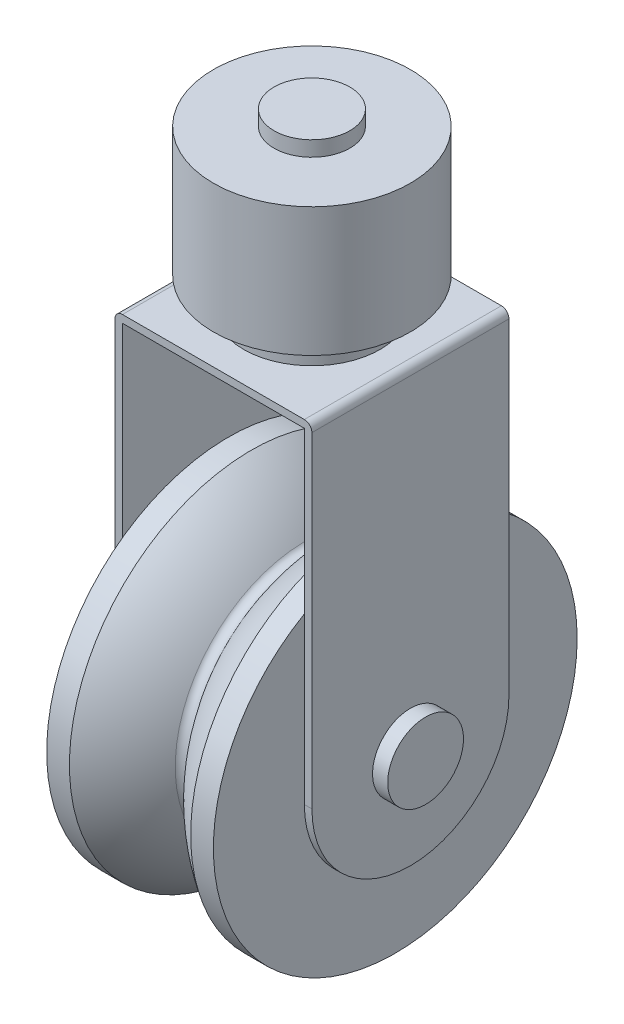
SolidWorks part; units mm, degrees
ref_plane "前视基准面" through (0, 0, 0) normal (0, 0, 1) x (1, 0, 0)
ref_plane "上视基准面" through (0, 0, 0) normal (0, 1, 0) x (1, 0, 0)
ref_plane "右视基准面" through (0, 0, 0) normal (1, 0, 0) x (0, 0, -1)
other "Configuration Table"
sketch "草图1" plane through (0, 0, 0) normal (0, 0, 1) x (1, 0, 0)
  line L0 (0, 0) -> (0, 16)
  line L1 (8, 24) -> (11, 24)
  line L2 (11, 24) -> (11, 0)
  line L3 (11, 0) -> (-11, 0)
  line L4 (11, 24) -> (8, 24)
  line L5 (-11, 24) -> (-11, 0)
  line L6 (-8, 24) -> (-11, 24)
  spline S0 degree 2 poles (0, 16) (3.2003, 21.0713) (8, 24) knots 0 0 0 0.822363 0.822363 0.822363
  spline S1 degree 2 poles (0, 16) (-3.2003, 21.0713) (-8, 24) knots 0 0 0 0.822363 0.822363 0.822363
  dimension "D1" = 24
  dimension "D2" = 11
revolve "旋转1" add sketch "草图1" angle 360 about L3 region at (-5.8476, 10.9127, 0) region at (5.8476, 10.9127, 0)
fillet "圆角1" radius 1 1 edges at (0, 0, -16)
sketch "草图2" plane through (0, 0, 0) normal (0, 0, 1) x (1, 0, 0)
  line L2 (-12, 2) -> (-12, 43)
  line L3 (-12, 2) -> (-12, 0)
  line L4 (-13, 2) -> (-13, 44)
  line L5 (-13, 44) -> (13, 44)
  line L6 (0, 0) -> (0, 44)
  line L7 (-12, 43) -> (12, 43)
  line L14 (12, 2) -> (12, 0)
  line L20 (12, 2) -> (12, 43)
  line L21 (13, 2) -> (13, 44)
  line L24 (-13, 2) -> (-13, 0)
  line L25 (-13, 0) -> (-12, 0)
  line L26 (13, 2) -> (13, 0)
  line L27 (13, 0) -> (12, 0)
  point P23 (0, 43)
  dimension "D1" = 67
  dimension "D2" = 1
  dimension "D3" = 1
extrude "凸台-拉伸1" add sketch "草图2" along normal mid plane 26 separate body contours L4 L3 L2 L7 L6 L5 | L21 L5 L6 L7 L20 L14 region at (-12.4588, 1, 0) region at (0.4588, 43.5, 0)
sketch "草图4" plane through (13, 0, 0) normal (1, 0, 0) x (0, 0, -1)
  line L0 (-13, 0) -> (13, 0)
  line L1 (-13, 0) -> (13, 0) construction
  arc A0 (13, 0) -> (-13, 0) centre (0, 0) cw
  line M4 (-13, 0) -> (13, 0)
extrude "凸台-拉伸3" add sketch "草图4" against normal up to surface (1 mm away) separate body contours A0 M4 region at (13, -5.5174, 0) up to face at (12, 21.5, 0)
sketch "草图5" plane through (13, 0, 0) normal (1, 0, 0) x (0, 0, -1)
  circle A0 centre (0, 0) radius 5
extrude "凸台-拉伸4" add sketch "草图5" against normal up to surface (2 mm away) and the other way blind 2 up to face at (11, 0, -24)
mirror "镜向9" about plane through (0, 0, 0) normal (1, 0, 0) of bodies 111
sketch "草图8" plane through (0, 44, 0) normal (0, 1, 0) x (1, 0, 0)
  circle A0 centre (0, 0) radius 9
extrude "凸台-拉伸5" add sketch "草图8" along normal blind 4
sketch "草图9" plane through (0, 48, 0) normal (0, 1, 0) x (1, 0, 0)
  circle A0 centre (0, 0) radius 13
extrude "凸台-拉伸6" add sketch "草图9" along normal blind 17
sketch "草图10" plane through (0, 65, 0) normal (0, 1, 0) x (1, 0, 0)
  circle A0 centre (0, 0) radius 5
extrude "凸台-拉伸7" add sketch "草图10" along normal blind 2
fillet "圆角3" radius 1 2 edges at (13, 44, 0) (-13, 44, 0)
sketch "草图11" plane through (0, 0, 0) normal (1, 0, 0) x (0, 0, -1)
  circle A0 centre (0, 0) radius 17.5
